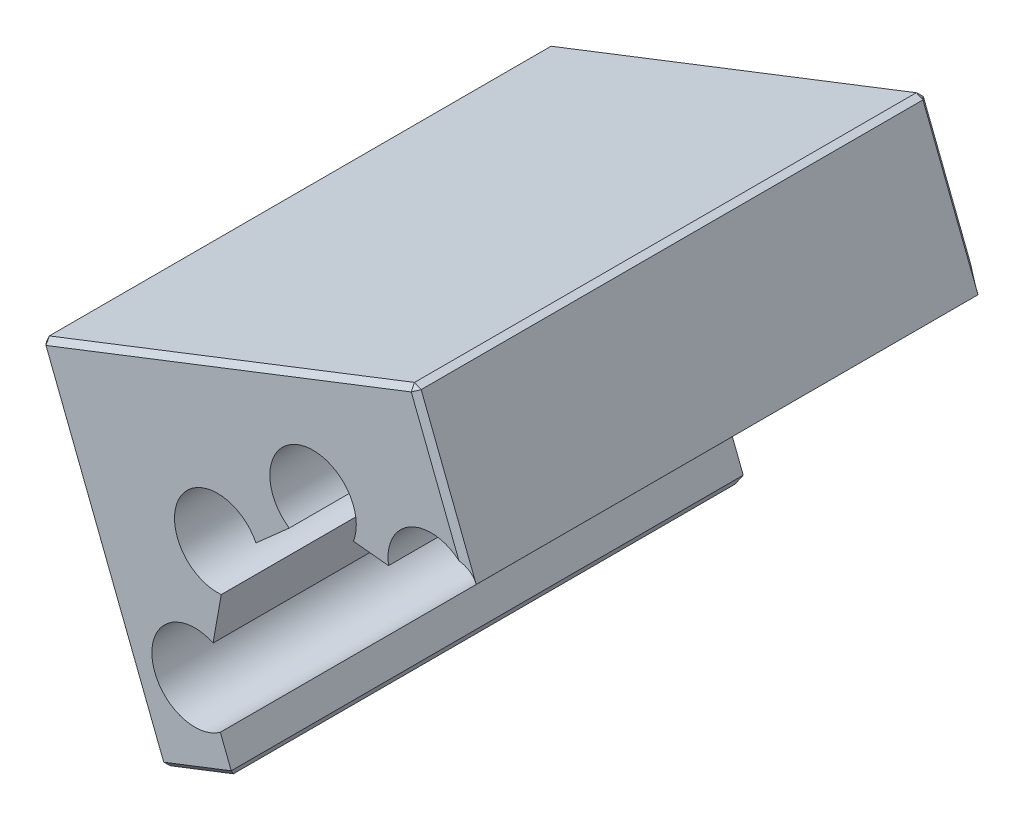
SolidWorks part; units mm, degrees
ref_plane "前基準面" through (0, 0, 0) normal (0, 0, 1) x (1, 0, 0)
ref_plane "上基準面" through (0, 0, 0) normal (0, 1, 0) x (1, 0, 0)
ref_plane "右基準面" through (0, 0, 0) normal (1, 0, 0) x (0, 0, -1)
sketch "草圖1" plane through (0, 0, -1.4732) normal (0, 0, 1) x (1, 0, 0)
  line L0 (-121.0055, -94.6668) -> (-109.956, -32.2463) construction
  line L1 (-109.956, -32.2463) -> (-63.2989, 9.2018) construction
  line L2 (-63.2989, 9.2018) -> (-5.7089, 3.2255) construction
  line L3 (-121.0055, -94.6668) -> (-112.1178, -75.6402) construction
  line L4 (-112.1178, -75.6402) -> (-108.1397, -53.1676)
  line L5 (-108.1397, -53.1676) -> (-109.956, -32.2463) construction
  line L6 (-109.956, -32.2463) -> (-91.1815, -22.8379) construction
  line L7 (-91.1815, -22.8379) -> (-74.9152, -8.4262)
  line L8 (-74.9152, -8.4262) -> (-63.2989, 9.2018) construction
  line L9 (-63.2989, 9.2018) -> (-43.5799, 1.6622) construction
  line L10 (-43.5799, 1.6622) -> (-26.446, -0.0869)
  line L11 (-26.446, -0.0869) -> (-5.7089, 3.2255) construction
  line L12 (-108.5754, -111.5928) -> (-102.3514, -127.5624)
  line L13 (-62.8813, -163.0069) -> (46.0586, -442.5281) construction
  line L14 (13.8576, 10.8513) -> (-13.9295, 82.1483)
  line L15 (-102.3514, -127.5624) -> (-137.6384, -141.3151)
  line L16 (-137.6384, -141.3151) -> (-196.9331, 10.825)
  line L17 (-196.9331, 10.825) -> (-13.9295, 82.1483)
  arc A1 (-112.1178, -75.6402) -> (-108.5754, -111.5928) centre (-121.0055, -94.6668) ccw
  arc A2 (-91.1815, -22.8379) -> (-108.1397, -53.1676) centre (-109.956, -32.2463) ccw
  arc A3 (-43.5799, 1.6622) -> (-74.9152, -8.4262) centre (-63.2989, 9.2018) ccw
  arc A4 (13.8576, 10.8513) -> (-26.446, -0.0869) centre (-5.7089, 3.2255) ccw
  dimension "D1" = 15
  dimension "D2" = 15
  dimension "D3" = 15
  dimension "D4" = 15
  dimension "D5" = 15
  dimension "D6" = 15
extrude "填料-伸長2" add sketch "草圖1" against normal blind 250
chamfer "導角1" distance 2.5 angle 45 12 edges at (-105.4313, 46.4867, -251.4732) (-0.036, 46.4998, -251.4732) (-13.9295, 82.1483, -126.4732) (-167.2857, -65.245, -251.4732) (-196.9331, 10.825, -126.4732) (-102.3514, -127.5624, -126.4732) (-119.9949, -134.4387, -251.4732) (-137.6384, -141.3151, -126.4732) (-119.9949, -134.4387, -1.4732) (-167.2857, -65.245, -1.4732) (-105.4313, 46.4867, -1.4732) (-0.036, 46.4998, -1.4732)
equation "\"ㄉ200\"=10"
